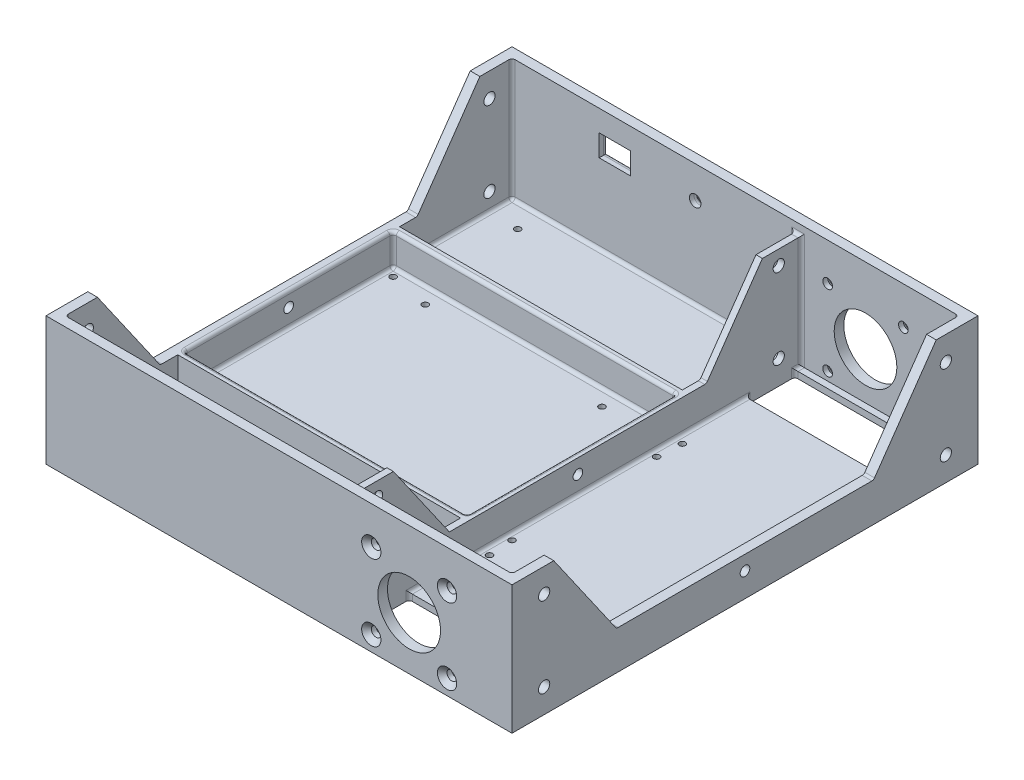
SolidWorks part; units mm, degrees
ref_plane "Спереди" through (0, 0, 0) normal (0, 0, 1) x (1, 0, 0)
ref_plane "Сверху" through (0, 0, 0) normal (0, 1, 0) x (1, 0, 0)
ref_plane "Справа" through (0, 0, 0) normal (1, 0, 0) x (0, 0, -1)
sketch "Эскиз1" plane through (0, 0, 0) normal (0, 1, 0) x (1, 0, 0)
  line L1 (-145, -145) -> (145, -145)
  line L2 (-145, -145) -> (-145, 145)
  line L3 (-145, 145) -> (145, 145)
  line L4 (145, -145) -> (145, 145)
  line L5 (0, 145) -> (0, -145) construction
  line L6 (-145, 0) -> (145, 0) construction
  point P0 (0, 0)
  dimension "D1" = 290
  dimension "D2" = 290
extrude "Бобышка-Вытянуть1" add sketch "Эскиз1" along normal blind 4
sketch "Эскиз2" plane through (0, 4, 0) normal (0, 1, 0) x (1, 0, 0)
  line L2 (145, 145) -> (145, 0.2395)
  line L5 (0, 0) -> (241.6766, 0) construction
  line L8 (145, -145) -> (145, 0.2395)
  line L11 (139, 139) -> (139, -139)
  line L13 (145, 145) -> (-145, 145) construction
  line L17 (145, 145) -> (-139, 145)
  line L18 (-139, 145) -> (-139, 139)
  line L19 (-139, 139) -> (139, 139)
  line L24 (-145, 145) -> (-145, -145) construction
  line L25 (-139, -139) -> (139, -139)
  line L30 (-139, -145) -> (-139, -139)
  line L35 (145, -145) -> (-139, -145)
  point P14 (139, 0)
  dimension "D1" = 6
  dimension "D3" = 6
  dimension "D9" = 6
extrude "Бобышка-Вытянуть2" add sketch "Эскиз2" along normal blind 76
sketch "Эскиз4" plane through (0, 4, 0) normal (0, 1, 0) x (1, 0, 0)
  line L0 (-145, -145) -> (-139, -145) construction
  line L1 (-145, 145) -> (-139, 145)
  line L2 (-145, 145) -> (-145, -145)
  line L3 (-145, -145) -> (-139, -145)
  line L4 (-139, 145) -> (-139, -145)
  dimension "D1" = 6
extrude "Бобышка-Вытянуть3" add sketch "Эскиз4" along normal up to surface (76 mm away) up to face at (1.5, 80, 0)
sketch "Эскиз17" plane through (0, 0, 145) normal (0, 0, 1) x (1, 0, 0)
  line L0 (81, 114.7773) -> (81, 33) construction
  line L1 (81, 33) -> (205.181, 33) construction
  line L2 (145, 80) -> (145, 0) construction
  line L3 (-145, 0) -> (145, 0) construction
  line L6 (57.43, 9.43) -> (104.57, 9.43) construction
  line L7 (57.43, 9.43) -> (57.43, 56.57) construction
  line L8 (57.43, 56.57) -> (104.57, 56.57) construction
  line L9 (104.57, 9.43) -> (104.57, 56.57) construction
  line L10 (81, 56.57) -> (81, 9.43) construction
  line L11 (57.43, 33) -> (104.57, 33) construction
  circle A0 centre (81, 33) radius 19.5
  circle A1 centre (57.43, 56.57) radius 3
  circle A4 centre (104.57, 56.57) radius 3
  circle A5 centre (104.57, 9.43) radius 3
  circle A6 centre (57.43, 9.43) radius 3
  dimension "D3" = 39
  dimension "D5" = 6
  dimension "D2" = 33
  dimension "D1" = 64
  dimension "D4" = 47.14
extrude "Вырез-Вытянуть12" cut sketch "Эскиз17" against normal through all both and the other way through all contours A0 | A1 | A4 | A5 | A6 region at (81, 33, 145) region at (57.43, 56.57, 145) region at (104.57, 56.57, 145) region at (104.57, 9.43, 145) region at (57.43, 9.43, 145)
sketch "Эскиз18" plane through (0, 4, 0) normal (0, 1, 0) x (1, 0, 0)
  line L0 (41, 0) -> (179.6266, 0) construction
  line L1 (-21, 118.2107) -> (-21, -110.4846) construction
  line L2 (145, -145) -> (145, 145) construction
  line L7 (37, -145) -> (41, -145)
  line L8 (37, -145) -> (37, 145)
  line L9 (37, 145) -> (41, 145)
  line L10 (41, -145) -> (41, 145)
  line L11 (39, 145) -> (39, -145) construction
  line L12 (37, 0) -> (41, 0) construction
  line L20 (145, 145) -> (-145, 145) construction
  point P16 (39, 0)
  dimension "D1" = 4
  dimension "D2" = 104
extrude "Бобышка-Вытянуть4" add sketch "Эскиз18" along normal blind 70
sketch "Эскиз19" plane through (145, 0, 0) normal (1, 0, 0) x (0, 0, -1)
  line L0 (0, 117.0161) -> (0, 24) construction
  line L1 (0, 24) -> (182.1669, 24) construction
  line L2 (-145, 0) -> (145, 0) construction
  line L3 (-80, 24) -> (80, 24)
  line L4 (80, 24) -> (119, 80)
  line L5 (-145, 80) -> (145, 80) construction
  line L6 (119, 80) -> (-119, 80)
  line L7 (145, 80) -> (145, 0) construction
  line L8 (-80, 24) -> (-119, 80)
  point P14 (0, 80)
  dimension "D1" = 24
  dimension "D2" = 26
  dimension "D3" = 160
extrude "Вырез-Вытянуть13" cut sketch "Эскиз19" against normal through all both and the other way through all
sketch "Эскиз14" plane through (0, 4, 0) normal (0, 1, 0) x (1, 0, 0)
  line L0 (81, 159.053) -> (81, -165.8467) construction
  line L2 (145, 145) -> (-145, 145) construction
  line L3 (41, 105) -> (121, 105)
  line L4 (41, 105) -> (41, 135)
  line L5 (41, 135) -> (121, 135)
  line L6 (121, 105) -> (121, 135)
  line L7 (81, 135) -> (81, 105) construction
  line L8 (41, 120) -> (121, 120) construction
  line L9 (0, 0) -> (180.733, 0) construction
  line L10 (41, -135) -> (121, -135)
  line L11 (121, -105) -> (121, -135)
  line L12 (41, -105) -> (121, -105)
  line L13 (41, -105) -> (41, -135)
  line L14 (145, 80) -> (145, -80) construction
  point P4 (81, 120)
  dimension "D1" = 64
  dimension "D2" = 80
  dimension "D3" = 30
  dimension "D4" = 10
extrude "Вырез-Вытянуть9" cut sketch "Эскиз14" against normal blind 20
sketch "Эскиз20" plane through (0, 4, 0) normal (0, 1, 0) x (1, 0, 0)
  line L0 (37, 139) -> (37, -139) construction
  line L1 (-139, 139) -> (37, 139)
  line L2 (-139, 139) -> (-139, 69)
  line L3 (-139, 69) -> (37, 69)
  line L4 (37, 139) -> (37, 69)
  line L5 (0, 0) -> (228.0193, 0) construction
  line L6 (37, -139) -> (37, -69)
  line L7 (-139, -69) -> (37, -69)
  line L8 (-139, -139) -> (-139, -69)
  line L9 (-139, -139) -> (37, -139)
  dimension "D1" = 70
extrude "Вытянуть-Тонкостенный1" add sketch "Эскиз20" along normal blind 20 thin thin type one direction wall 4
sketch "Эскиз15" plane through (-145, 0, 0) normal (-1, 0, 0) x (0, 0, 1)
  line L0 (0, 107.7828) -> (0, 40) construction
  line L1 (0, 40) -> (185.6693, 40) construction
  line L2 (-145, 0) -> (145, 0) construction
  line L3 (-171.7731, 65) -> (170.5378, 65) construction
  circle A0 centre (0, 65) radius 3
  circle A1 centre (125, 65) radius 3.5
  circle A2 centre (-125, 65) radius 3.5
  circle A3 centre (-125, 15) radius 3.5
  circle A4 centre (125, 15) radius 3.5
  circle A5 centre (0, 15) radius 3
  dimension "D3" = 6
  dimension "D4" = 125
  dimension "D1" = 40
  dimension "D2" = 25
extrude "Вырез-Вытянуть10" cut sketch "Эскиз15" against normal through all both and the other way through all
sketch "Эскиз7" plane through (0, 4, 0) normal (0, 1, 0) x (1, 0, 0)
  line L0 (0, 112.8082) -> (0, 0) construction
  line L1 (0, 0) -> (196.7673, 0) construction
  line L7 (-139, -139) -> (-139, -69) construction
  line L8 (-109, -55) -> (1, -55) construction
  line L9 (-109, -55) -> (-109, 55) construction
  line L10 (-109, 55) -> (1, 55) construction
  line L15 (1, -55) -> (1, 55) construction
  line L16 (-54, 55) -> (-54, -55) construction
  line L17 (-109, 0) -> (1, 0) construction
  line L22 (-139, 65) -> (37, 65) construction
  line L23 (-139, 65) -> (-139, -65) construction
  line L24 (139, 139) -> (139, -139) construction
  line L25 (41, 139) -> (139, 139) construction
  line L26 (90, 139) -> (90, -164.4799) construction
  line L28 (45, -45) -> (135, -45) construction
  line L29 (45, -45) -> (45, 45) construction
  line L30 (45, 45) -> (135, 45) construction
  line L31 (135, -45) -> (135, 45) construction
  line L32 (90, 45) -> (90, -45) construction
  line L33 (45, 0) -> (135, 0) construction
  line L34 (-139, 139) -> (37, 139) construction
  line L35 (-139, 119) -> (-139, 80) construction
  line L36 (-139, 99.5) -> (-51, 99.5) construction
  line L37 (-51, 99.5) -> (-51, 139) construction
  line L38 (-121, 74.5) -> (19, 74.5) construction
  line L39 (-121, 74.5) -> (-121, 124.5) construction
  line L40 (-121, 124.5) -> (19, 124.5) construction
  line L41 (19, 74.5) -> (19, 124.5) construction
  line L42 (-51, 124.5) -> (-51, 74.5) construction
  line L43 (-121, 99.5) -> (19, 99.5) construction
  circle A25 centre (-109, 55) radius 1.9
  circle A26 centre (1, 55) radius 1.9
  circle A27 centre (1, -55) radius 1.9
  circle A28 centre (-109, -55) radius 1.9
  circle A29 centre (-134, 60) radius 1.9
  circle A30 centre (-134, -60) radius 1.9
  circle A31 centre (134, 134) radius 1.9
  circle A32 centre (134, -134) radius 1.9
  circle A33 centre (134, -60) radius 1.9
  circle A34 centre (134, 60) radius 1.9
  circle A35 centre (46, -60) radius 1.9
  circle A36 centre (46, 60) radius 1.9
  circle A37 centre (45, 45) radius 1.9
  circle A38 centre (135, 45) radius 1.9
  circle A39 centre (45, -45) radius 1.9
  circle A40 centre (135, -45) radius 1.9
  circle A41 centre (-121, 124.5) radius 1.9
  circle A42 centre (-121, 74.5) radius 1.9
  circle A43 centre (19, 124.5) radius 1.9
  circle A44 centre (19, 74.5) radius 1.9
  circle A45 centre (19, -74.5) radius 1.9
  circle A46 centre (19, -124.5) radius 1.9
  circle A47 centre (-121, -74.5) radius 1.9
  circle A48 centre (-121, -124.5) radius 1.9
  point P4 (-54, 0)
  point P40 (90, 0)
  dimension "D4" = 30
  dimension "D5" = 5
  dimension "D12" = 90
  dimension "D3" = 3.8
  dimension "D6" = 5
  dimension "D7" = 120
  dimension "D8" = 5
  dimension "D9" = 5
  dimension "D10" = 268
  dimension "D17" = 93
  dimension "D18" = 46
  dimension "D19" = 134
  dimension "D20" = 134
  dimension "D1" = 110
  dimension "D2" = 110
  dimension "D11" = 90
  dimension "D13" = 140
  dimension "D14" = 50
  dimension "D15" = 60
  dimension "D16" = 134
extrude "Вырез-Вытянуть3" cut sketch "Эскиз7" against normal blind 10
fillet "Скругление1" radius 2 47 edges at (-51, 4, 69) (-51, 4, 65) (-51, 24, 65) (-139, 14, 65) (37, 14, 65) (-51, 4, -69) (-51, 4, -65) (39, 24, -80) (-139, 14, -65) (-51, 24, -65) (37, 14, -65) (41, 2, 135) (121, 2, 135) (121, 2, 105) (41, 2, 105) (121, 2, -135) (41, 2, -135) (41, 2, -105) (121, 2, -105) (142, 24, 80) (142, 24, -80) (41, 4, -137) (41, 4, 0) (41, 4, 137) (37, 4, 104) (37, 4, 0) (37, 4, -104) (39, 74, -139) (37, 39, -139) (41, 39, -139) (-139, 4, -104) (-139, 4, 0) (-139, 4, 104) (-51, 4, -139) (139, 4, 0) (-51, 4, 139) (-139, 42, 139) (139, 42, 139) (139, 42, -139) (39, 74, 139) (37, 39, 139) (41, 39, 139) (-142, 24, -80) (-139, 42, -139) (-139, 24, 0) (37, 24, 0) (-142, 24, 80)
sketch "Эскиз21" plane through (0, 0, -145) normal (0, 0, -1) x (-1, 0, 0)
  line L0 (145, 80) -> (145, 0) construction
  line L1 (-145, 80) -> (145, 80) construction
  line L3 (65.25, 53.25) -> (84.75, 53.25)
  line L4 (65.25, 53.25) -> (65.25, 66.75)
  line L5 (65.25, 66.75) -> (84.75, 66.75)
  line L6 (84.75, 53.25) -> (84.75, 66.75)
  line L7 (75, 66.75) -> (75, 53.25) construction
  line L8 (65.25, 60) -> (84.75, 60) construction
  circle A0 centre (25, 60) radius 3.6
  point P6 (75, 60)
  dimension "D1" = 7.2
  dimension "D2" = 120
  dimension "D3" = 20
  dimension "D4" = 19.5
  dimension "D5" = 13.5
  dimension "D6" = 20
  dimension "D7" = 70
extrude "Вырез-Вытянуть14" cut sketch "Эскиз21" against normal blind 10
chamfer "Фаска1" distance 2 angle 45 5 edges at (-84.75, 60, -145) (-75, 66.75, -145) (-65.25, 60, -145) (-75, 53.25, -145) (-28.6, 60, -145)
fillet "Скругление2" radius 3 5 edges at (-21.4, 60, -143) (-84.75, 60, -143) (-75, 66.75, -143) (-65.25, 60, -143) (-75, 53.25, -143)
chamfer "Фаска2" distance 3 angle 45 8 edges at (54.43, 9.43, 145) (101.57, 56.57, 145) (54.43, 56.57, 145) (107.57, 9.43, -145) (60.43, 9.43, -145) (107.57, 56.57, -145) (60.43, 56.57, -145) (101.57, 9.43, 145)
